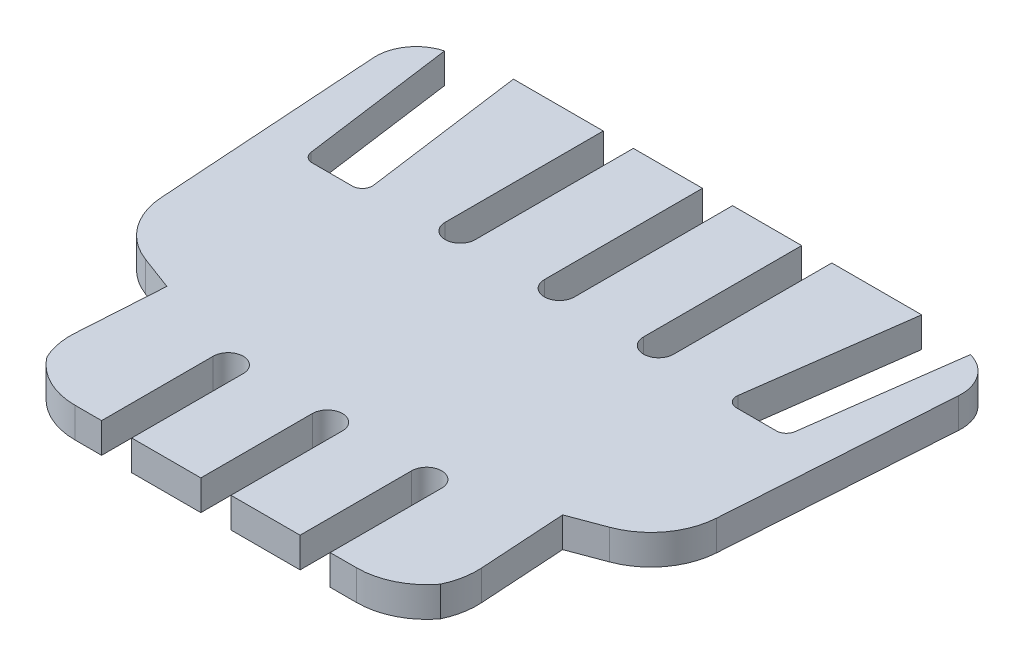
SolidWorks part; units mm, degrees
ref_plane "Front Plane" through (0, 0, 0) normal (0, 0, 1) x (1, 0, 0)
ref_plane "Top Plane" through (0, 0, 0) normal (0, 1, 0) x (1, 0, 0)
ref_plane "Right Plane" through (0, 0, 0) normal (1, 0, 0) x (0, 0, -1)
sketch "Sketch1" plane through (0, 0, 0) normal (0, 1, 0) x (1, 0, 0)
  line L0 (-1.5, 15.76) -> (-1.5, 0)
  line L1 (1.5, 0) -> (1.5, 15.76)
  line L2 (1.5, 15.76) -> (8.39, 15.76)
  line L3 (8.39, 15.76) -> (8.39, 0)
  line L4 (11.39, 0) -> (11.39, 15.76)
  line L5 (11.39, 15.76) -> (20.345, 15.76)
  line L6 (20.345, 15.76) -> (18, -1.5)
  line L7 (18, -1.5) -> (24, -1.5)
  line L8 (24, -1.5) -> (26.2091, 14.76)
  line L9 (26.2091, 14.76) -> (29.4391, 14.76)
  line L10 (29.4391, 14.76) -> (27.375, -16.54)
  line L11 (27.375, -16.54) -> (19.725, -19.4)
  line L12 (19.725, -19.4) -> (20.405, -30.24)
  line L13 (20.405, -30.24) -> (17.97, -34.24)
  line L14 (17.97, -34.24) -> (11.39, -34.24)
  line L15 (11.39, -34.24) -> (11.39, -23.125)
  line L16 (8.39, -23.125) -> (8.39, -34.24)
  line L17 (8.39, -34.24) -> (1.5, -34.24)
  line L18 (1.5, -34.24) -> (1.5, -23.125)
  line L19 (-1.5, -23.125) -> (-1.5, -34.24)
  line L20 (0, -55) -> (0, 55) construction
  line L21 (-8.39, -34.24) -> (-1.5, -34.24)
  line L22 (-8.39, -23.125) -> (-8.39, -34.24)
  line L23 (-11.39, -34.24) -> (-11.39, -23.125)
  line L24 (-17.97, -34.24) -> (-11.39, -34.24)
  line L25 (-20.405, -30.24) -> (-17.97, -34.24)
  line L26 (-19.725, -19.4) -> (-20.405, -30.24)
  line L27 (-27.375, -16.54) -> (-19.725, -19.4)
  line L28 (-29.4391, 14.76) -> (-27.375, -16.54)
  line L29 (-26.2091, 14.76) -> (-29.4391, 14.76)
  line L30 (-24, -1.5) -> (-26.2091, 14.76)
  line L31 (-18, -1.5) -> (-24, -1.5)
  line L32 (-20.345, 15.76) -> (-18, -1.5)
  line L33 (-11.39, 15.76) -> (-20.345, 15.76)
  line L34 (-11.39, 0) -> (-11.39, 15.76)
  line L35 (-8.39, 15.76) -> (-8.39, 0)
  line L36 (-1.5, 15.76) -> (-8.39, 15.76)
  arc A0 (-1.5, 0) -> (1.5, 0) centre (0, 0) ccw
  arc A1 (8.39, 0) -> (11.39, 0) centre (9.89, 0) ccw
  arc A2 (11.39, -23.125) -> (8.39, -23.125) centre (9.89, -23.125) ccw
  arc A3 (1.5, -23.125) -> (-1.5, -23.125) centre (0, -23.125) ccw
  arc A4 (-11.39, -23.125) -> (-8.39, -23.125) centre (-9.89, -23.125) cw
  arc A5 (-8.39, 0) -> (-11.39, 0) centre (-9.89, 0) cw
  point P6 (0, -1.5)
  point P30 (0, -21.625)
  point P36 (9.89, -1.5)
  dimension "D1" = 1.5
  dimension "D2" = 17.26
  dimension "D3" = 12.615
  dimension "D4" = 16.78
  dimension "D5" = 40.69
  dimension "D6" = 6
  dimension "D7" = 1
  dimension "D8" = 3.23
  dimension "D9" = 31.3
  dimension "D10" = 19.725
  dimension "D11" = 20.405
  dimension "D12" = 50
  dimension "D13" = 4
  dimension "D14" = 14.84
  dimension "D15" = 27.375
  dimension "D16" = 6.58
  dimension "D17" = 82.263
extrude "Boss-Extrude1" add sketch "Sketch1" along normal blind 3
fillet "Fillet1" radius 4 2 edges at (-29.4391, 1.5, -14.76) (29.4391, 1.5, -14.76)
fillet "Fillet2" radius 1 4 edges at (24, 1.5, 1.5) (18, 1.5, 1.5) (-18, 1.5, 1.5) (-24, 1.5, 1.5)
fillet "Fillet3" radius 7 6 edges at (-17.97, 1.5, 34.24) (17.97, 1.5, 34.24) (-20.405, 1.5, 30.24) (20.405, 1.5, 30.24) (-27.375, 1.5, 16.54) (27.375, 1.5, 16.54)
